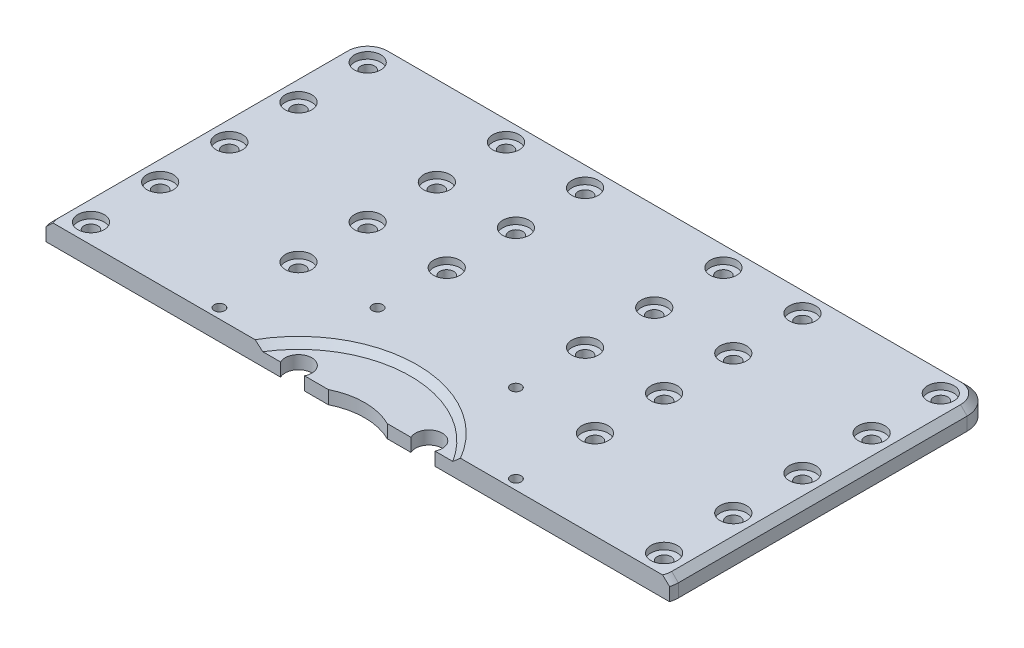
SolidWorks part; units mm, degrees
material "ABS"
ref_plane "正面" through (0, 0, 0) normal (0, 0, 1) x (1, 0, 0)
ref_plane "平面" through (0, 0, 0) normal (0, 1, 0) x (1, 0, 0)
ref_plane "右側面" through (0, 0, 0) normal (1, 0, 0) x (0, 0, -1)
sketch "ｽｹｯﾁ1" plane through (0, 0, 0) normal (0, 1, 0) x (1, 0, 0)
  line L0 (-10.05, 0) -> (-39, 0)
  line L1 (-39, 0) -> (-47.5, 8.5)
  line L2 (-47.5, 8.5) -> (-47.5, 58)
  line L3 (-47.5, 58) -> (47.5, 58)
  line L4 (47.5, 58) -> (47.5, 8.5)
  line L5 (47.5, 8.5) -> (39, 0)
  line L6 (39, 0) -> (10.05, 0)
  line L7 (-10.05, 0) -> (0, 0) construction
  line L8 (0, 0) -> (10.05, 0) construction
  arc A0 (10.05, 0) -> (-10.05, 0) centre (0, 0) ccw
  dimension "D1" = 20.1
  dimension "D2" = 95
  dimension "D3" = 58
  dimension "D4" = 78
extrude "ﾎﾞｽ - 押し出し1" add sketch "ｽｹｯﾁ1" along normal blind 3
hole_wizard "M2 なべ頭ねじ用座ぐり穴1" positions "ｽｹｯﾁ2" profile "ｽｹｯﾁ3" counterbore size "M2" standard "ISO"
sketch "ｽｹｯﾁ2" plane through (0, 3, 0) normal (0, 1, 0) x (1, 0, 0)
  line L0 (-43.5, 54) -> (-22.5, 54) construction
  line L2 (47.5, 58) -> (-47.5, 58) construction
  line L3 (-47.5, 58) -> (-47.5, 8.5) construction
  point P0 (-43.5, 54)
  point P2 (-22.5, 54)
  dimension "D1" = 4
  dimension "D2" = 4
  dimension "D3" = 21
sketch "ｽｹｯﾁ3" plane through (-43.5, 3, -54) normal (1, 0, 0) x (0, 0, 1)
  line L0 (0, 0) -> (0, 4.6309)
  line L1 (0, 4.6309) -> (1.05, 4)
  line L2 (1.05, 4) -> (1.05, 1)
  line L3 (1.05, 1) -> (2, 1)
  line L4 (2, 1) -> (2, 0)
  line L5 (2, 0) -> (0, 0)
  line L10 (0, 4.6309) -> (-1.05, 4) construction
  line L11 (0, -6.35) -> (0, 107.95) construction
  dimension "穴の直径" = 2.1
  dimension "穴の深さ" = 4
  dimension "座ぐり穴の直径" = 4
  dimension "座ぐり穴の深さ" = 1
  dimension "ﾄﾞﾘﾙ角度" = 118
pattern_linear "直線ﾊﾟﾀｰﾝ1" count 3 spacing 33 along (1, 0, 0) of "M2 なべ頭ねじ用座ぐり穴1"
pattern_linear "直線ﾊﾟﾀｰﾝ2" count 3 spacing 10.5 along (0, 0, 1) of "M2 なべ頭ねじ用座ぐり穴1", "直線ﾊﾟﾀｰﾝ1"
pattern_linear "直線ﾊﾟﾀｰﾝ3" count 2 spacing 31.5 along (0, 0, 1) of "M2 なべ頭ねじ用座ぐり穴1"
hole_wizard "M2 ねじ穴1" positions "ｽｹｯﾁ4" profile "ｽｹｯﾁ5" tap size "M2" standard "ISO"
sketch "ｽｹｯﾁ4" plane through (0, 3, 0) normal (0, 1, 0) x (1, 0, 0)
  line L0 (-22.5, 10.5) -> (-22.5, 22.5) construction
  line L1 (-22.5, 22.5) -> (-10.5, 22.5) construction
  line L2 (-10.5, 22.5) -> (-10.5, 33) construction
  line L4 (-39, 0) -> (-10.05, 0) construction
  point P0 (-10.5, 22.5)
  point P2 (-22.5, 10.5)
  dimension "D1" = 10.5
sketch "ｽｹｯﾁ5" plane through (-10.5, 3, -22.5) normal (1, 0, 0) x (0, 0, 1)
  line L0 (0, 0) -> (0, 6.4807)
  line L1 (0, 6.4807) -> (0.8, 6)
  line L2 (0.8, 6) -> (0.8, 0)
  line L5 (0.8, 0) -> (0, 0)
  line L10 (0, 6.4807) -> (-0.8, 6) construction
  line L11 (0, -6.35) -> (0, 107.95) construction
  dimension "ねじ下穴ﾄﾞﾘﾙ直径" = 1.6
  dimension "ねじ下穴ﾄﾞﾘﾙの深さ" = 6
  dimension "ﾄﾞﾘﾙ角度" = 118
cosmetic thread "穴のねじ山1" parameters "D1"=4, "D2"=2
cosmetic thread "穴のねじ山2" parameters "D1"=4, "D2"=2
hole_wizard "M2 なべ頭ねじ用座ぐり穴2" positions "ｽｹｯﾁ6" profile "ｽｹｯﾁ7" counterbore size "M2" standard "ISO"
sketch "ｽｹｯﾁ6" plane through (0, 3, 0) normal (0, 1, 0) x (1, 0, 0)
  line L0 (-43.5, 22.5) -> (-43.5, 12) construction
  line L3 (-43.5, 33) -> (-43.5, 22.5) construction
  point P0 (-43.5, 12)
sketch "ｽｹｯﾁ7" plane through (-43.5, 3, -12) normal (1, 0, 0) x (0, 0, 1)
  line L0 (0, 0) -> (0, 6.6309)
  line L1 (0, 6.6309) -> (1.05, 6)
  line L2 (1.05, 6) -> (1.05, 1)
  line L3 (1.05, 1) -> (2, 1)
  line L4 (2, 1) -> (2, 0)
  line L5 (2, 0) -> (0, 0)
  line L10 (0, 6.6309) -> (-1.05, 6) construction
  line L11 (0, -6.35) -> (0, 107.95) construction
  dimension "穴の直径" = 2.1
  dimension "穴の深さ" = 6
  dimension "座ぐり穴の直径" = 4
  dimension "座ぐり穴の深さ" = 1
  dimension "ﾄﾞﾘﾙ角度" = 118
mirror "ﾐﾗｰ1" about plane through (0, 0, 0) normal (1, 0, 0) of "M2 なべ頭ねじ用座ぐり穴2", "M2 ねじ穴1", "直線ﾊﾟﾀｰﾝ3"
cosmetic thread "穴のねじ山3" parameters "D1"=4, "D2"=2
cosmetic thread "穴のねじ山4" parameters "D1"=4, "D2"=2
sketch "ｽｹｯﾁ8" plane through (0, 3, 0) normal (0, 1, 0) x (1, 0, 0)
  circle A0 centre (0, 0) radius 17
  dimension "D1" = 34
extrude "ｶｯﾄ - 押し出し1" cut sketch "ｽｹｯﾁ8" against normal blind 1
sketch "ｽｹｯﾁ9" plane through (0, 2, 0) normal (0, 1, 0) x (1, 0, 0)
  line L0 (-9.8995, 9.8995) -> (0, 0) construction
  line L2 (-17, 0) -> (-10.05, 0) construction
  circle A0 centre (-9.8995, 9.8995) radius 2.025
  dimension "D1" = 4.05
  dimension "D2" = 45
  dimension "D3" = 14
extrude "ｶｯﾄ - 押し出し2" cut sketch "ｽｹｯﾁ9" against normal through all
pattern_circular "円形ﾊﾟﾀｰﾝ1" count 2 every 90 about axis through (0, 3, 0) along (0, -1, 0) of "ｶｯﾄ - 押し出し2"
fillet "ﾌｨﾚｯﾄ1" radius 4 6 edges at (-47.5, 1.5, -8.5) (-39, 1.5, 0) (39, 1.5, 0) (47.5, 1.5, -8.5) (47.5, 1.5, -58) (-47.5, 1.5, -58)
chamfer "面取り1" distance 1 angle 45 14 edges at (0, 3, -17) (27.1716, 3, 0) (38.8739, 3, -0.3045) (43.25, 3, -4.25) (47.1955, 3, -8.6261) (47.5, 3, -32.0784) (-27.1716, 3, 0) (46.3284, 3, -56.8284) (-38.8739, 3, -0.3045) (0, 3, -58) (-43.25, 3, -4.25) (-46.3284, 3, -56.8284) (-47.1955, 3, -8.6261) (-47.5, 3, -32.0784)
sketch "ｽｹｯﾁ11" plane through (0, 3, 0) normal (0, 1, 0) x (1, 0, 0)
  line L1 (-47.5, 9) -> (47.5, 9)
  line L2 (-47.5, 9) -> (-47.5, -9)
  line L3 (-47.5, -9) -> (47.5, -9)
  line L4 (47.5, 9) -> (47.5, -9)
  line L5 (-47.5, 9) -> (47.5, -9) construction
  line L6 (-47.5, -9) -> (47.5, 9) construction
  line L7 (-47.5, 10.1569) -> (-47.5, 54) construction
  circle A0 centre (-43.5, 12) radius 1.05 construction
  point P4 (0, 0)
  dimension "D1" = 3
extrude "ｶｯﾄ - 押し出し3" cut sketch "ｽｹｯﾁ11" against normal through all
